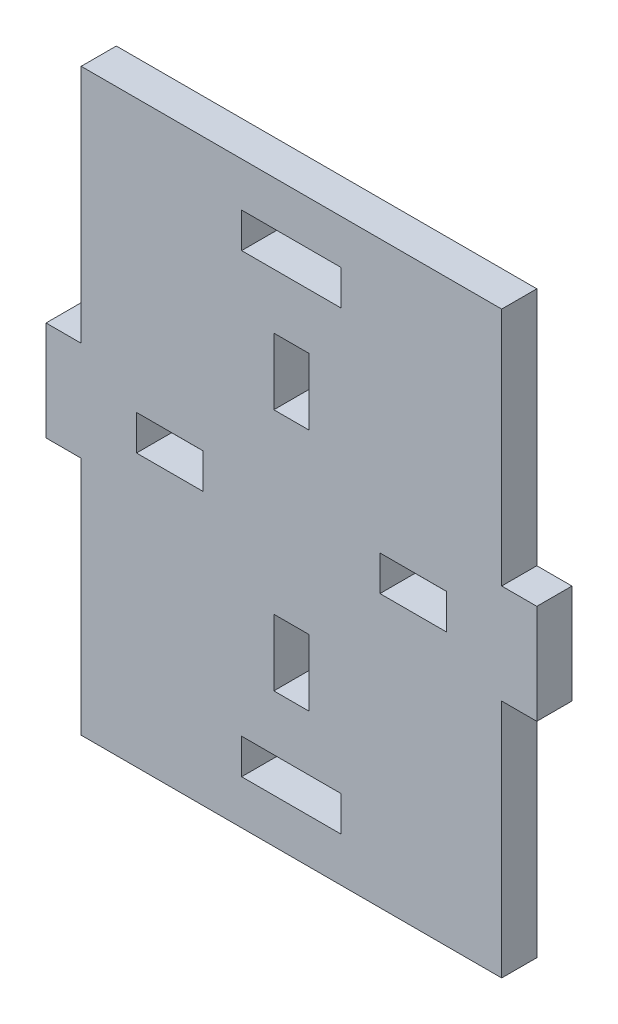
SolidWorks part; units mm, degrees
ref_plane "Front Plane" through (0, 0, 0) normal (0, 0, 1) x (1, 0, 0)
ref_plane "Top Plane" through (0, 0, 0) normal (0, 1, 0) x (1, 0, 0)
ref_plane "Right Plane" through (0, 0, 0) normal (1, 0, 0) x (0, 0, -1)
sketch "Sketch1" plane through (0, 0, 0) normal (0, 0, 1) x (1, 0, 0)
  line L0 (0, 0) -> (0, 21.675)
  line L1 (0, 21.675) -> (3.175, 21.675)
  line L2 (3.175, 21.675) -> (3.175, 30.675)
  line L3 (3.175, 30.675) -> (0, 30.675)
  line L4 (0, 30.675) -> (0, 52.35)
  line L5 (0, 52.35) -> (-38, 52.35)
  line L6 (-38, 52.35) -> (-38, 30.675)
  line L7 (-38, 30.675) -> (-41.175, 30.675)
  line L8 (-41.175, 30.675) -> (-41.175, 21.675)
  line L9 (-41.175, 21.675) -> (-38, 21.675)
  line L10 (-38, 21.675) -> (-38, 0)
  line L11 (-38, 0) -> (0, 0)
  line L12 (-19, 4) -> (-14.5, 4)
  line L13 (-14.5, 4) -> (-14.5, 7.175)
  line L14 (-14.5, 7.175) -> (-23.5, 7.175)
  line L15 (-23.5, 7.175) -> (-23.5, 4)
  line L16 (-23.5, 4) -> (-19, 4)
  line L17 (-19, 12.175) -> (-17.41, 12.175)
  line L18 (-17.41, 12.175) -> (-17.41, 18.175)
  line L19 (-17.41, 18.175) -> (-20.59, 18.175)
  line L20 (-20.59, 18.175) -> (-20.59, 12.175)
  line L21 (-20.59, 12.175) -> (-19, 12.175)
  line L22 (11.9114, 26.175) -> (-39.248, 26.175) construction
  line L23 (-19, 4) -> (-19, 0) construction
  line L24 (-41.175, 26.175) -> (3.175, 26.175) construction
  line L25 (-20.59, 40.175) -> (-19, 40.175)
  line L26 (-20.59, 34.175) -> (-20.59, 40.175)
  line L27 (-17.41, 34.175) -> (-20.59, 34.175)
  line L28 (-17.41, 40.175) -> (-17.41, 34.175)
  line L29 (-19, 40.175) -> (-17.41, 40.175)
  line L30 (-23.5, 48.35) -> (-19, 48.35)
  line L31 (-23.5, 45.175) -> (-23.5, 48.35)
  line L32 (-14.5, 45.175) -> (-23.5, 45.175)
  line L33 (-14.5, 48.35) -> (-14.5, 45.175)
  line L34 (-19, 48.35) -> (-14.5, 48.35)
  line L35 (-27, 26.175) -> (-27, 27.765)
  line L36 (-27, 27.765) -> (-33, 27.765)
  line L37 (-33, 27.765) -> (-33, 24.585)
  line L38 (-33, 24.585) -> (-27, 24.585)
  line L39 (-27, 24.585) -> (-27, 26.175)
  line L40 (-19, 40.35) -> (-19, 32.175) construction
  line L41 (-11, 24.585) -> (-11, 26.175)
  line L42 (-5, 24.585) -> (-11, 24.585)
  line L43 (-5, 27.765) -> (-5, 24.585)
  line L44 (-11, 27.765) -> (-5, 27.765)
  line L45 (-11, 26.175) -> (-11, 27.765)
  dimension "D1" = 3.175
  dimension "D2" = 3.18
  dimension "D3" = 9
  dimension "D4" = 6
  dimension "D5" = 5
  dimension "D6" = 3.175
  dimension "D7" = 9
  dimension "D8" = 19
  dimension "D9" = 4
  dimension "D10" = 38
  dimension "D11" = 3.18
  dimension "D12" = 6
  dimension "D13" = 5
extrude "Boss-Extrude1" add sketch "Sketch1" along normal mid plane 3.175
